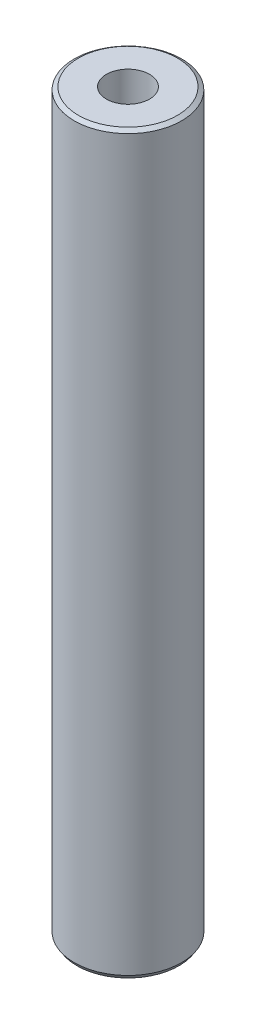
SolidWorks part; units mm, degrees
ref_plane "Front Plane" through (0, 0, 0) normal (0, 0, 1) x (1, 0, 0)
ref_plane "Top Plane" through (0, 0, 0) normal (0, 1, 0) x (1, 0, 0)
ref_plane "Right Plane" through (0, 0, 0) normal (1, 0, 0) x (0, 0, -1)
sketch "Sketch1" plane through (0, 0, 0) normal (0, 1, 0) x (1, 0, 0)
  circle A0 centre (0, 0) radius 40
  dimension "SHAFT_OD" = 80
extrude "Boss-Extrude1" add sketch "Sketch1" along normal blind 548.2626
sketch "Sketch2" plane through (0, 0, 0) normal (0, 1, 0) x (1, 0, 0)
  circle A0 centre (0, 0) radius 16.0517
  dimension "BORE_D" = 32.1034
extrude "Cut-Extrude1" cut sketch "Sketch2" along normal through all
chamfer "Chamfer1" distance 2.013 angle 56.71 2 edges at (0, 548.2626, 40) (0, 0, 40) first distance on face at (0, 548.2626, 40) first distance on face at (0, 0, 16.0517)
